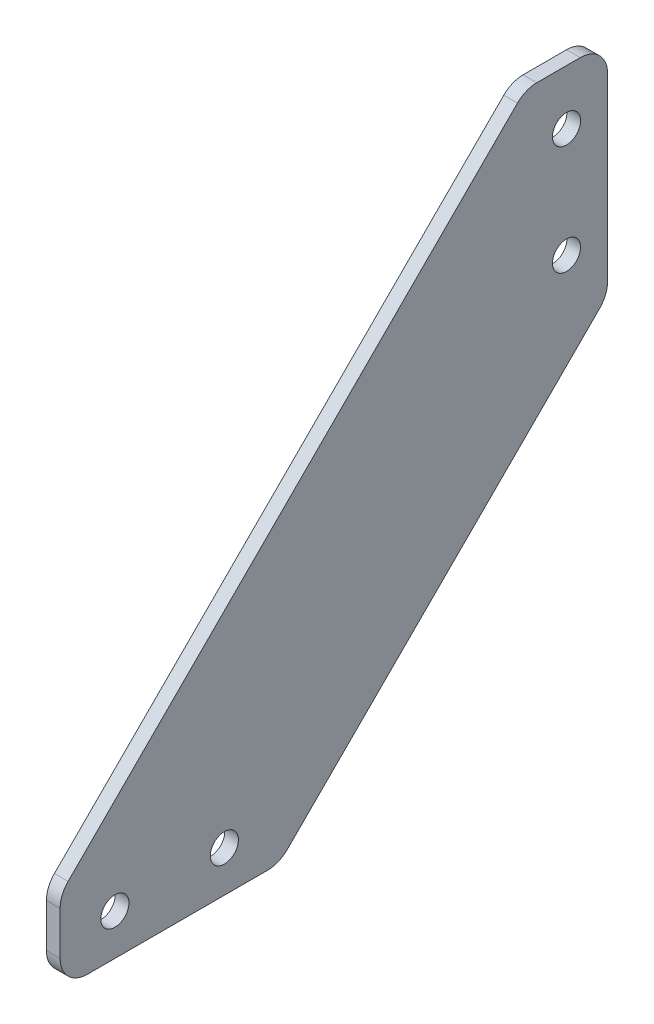
SolidWorks part; units mm, degrees
material "6061 Alloy"
ref_plane "Front Plane" through (0, 0, 0) normal (0, 0, 1) x (1, 0, 0)
ref_plane "Top Plane" through (0, 0, 0) normal (0, 1, 0) x (1, 0, 0)
ref_plane "Right Plane" through (0, 0, 0) normal (1, 0, 0) x (0, 0, -1)
sketch "Sketch1" plane through (0, 0, 0) normal (1, 0, 0) x (0, 0, -1)
  line L0 (0, 0) -> (0, 76.2) construction
  line L1 (0, 127) -> (-19.05, 127)
  line L2 (-19.05, 127) -> (-127, 19.05)
  line L3 (-127, 19.05) -> (-127, 0)
  line L4 (-127, 0) -> (-76.2, 0)
  line L5 (-76.2, 0) -> (0, 0) construction
  line L6 (0, 76.2) -> (0, 127)
  line L7 (-76.2, 0) -> (0, 76.2)
  line L8 (-127, 0) -> (0, 127) construction
  dimension "D1" = 45
  dimension "D2" = 127
  dimension "D3" = 19.05
  dimension "D4" = 50.8
extrude "1/8 in Sheet Metal" add sketch "Sketch1" along normal mid plane 3.175
ref_plane "Plane1" through (0, 9.525, 0) normal (0, -1, 0) x (-1, 0, 0)
ref_plane "Plane2" through (0, 0, 9.525) normal (0, 0, -1) x (-1, 0, 0)
ref_axis "Axis1" through (0, 9.525, 133.35) along (0, 0, -1)
ref_axis "Axis2" through (0, 72.375, 9.525) along (0, 1, 0)
hole_wizard "1/4 Clearance Hole1" positions "Sketch3" profile "Sketch4" hole size "1/4" standard "ANSI Inch" end condition through all
sketch "Sketch3" plane through (1.5875, 0, 0) normal (1, 0, 0) x (0, 0, -1)
  line L0 (-133.35, 9.525) -> (-74.9182, 9.525) construction
  line L1 (-9.525, 72.375) -> (-9.525, 133.35) construction
  line L2 (-127, 19.05) -> (-127, 0) construction
  line L3 (0, 127) -> (-19.05, 127) construction
  point P0 (-114.3, 9.525)
  point P4 (-88.9, 9.525)
  point P6 (-9.525, 88.9)
  point P10 (-9.525, 114.3)
  dimension "D1" = 25.4
  dimension "D2" = 25.4
  dimension "D3" = 12.7
  dimension "D4" = 12.7
sketch "Sketch4" plane through (1.5875, 9.525, 114.3) normal (0, 1, 0) x (0, 0, -1)
  line L0 (0, 0) -> (0, 3.175)
  line L1 (0, 3.175) -> (3.2639, 3.175)
  line L2 (3.2639, 3.175) -> (3.2639, 0)
  line L5 (3.2639, 0) -> (0, 0)
  line L11 (0, -6.35) -> (0, 107.95) construction
  dimension "Thru Hole Dia." = 6.5278
  dimension "Thru Hole Depth" = 3.175
fillet "Fillet 1/4 in" radius 6.35 6 edges at (0, 76.2, 0) (0, 127, 0) (0, 127, 19.05) (0, 19.05, 127) (0, 0, 76.2) (0, 0, 127)
chamfer "Chamfer 1/100 in" [suppressed] distance 0.254 angle 45
ref_plane "Center Plane" through (0, 0, 0) normal (0, -0.7071, 0.7071) x (1, 0, 0)
